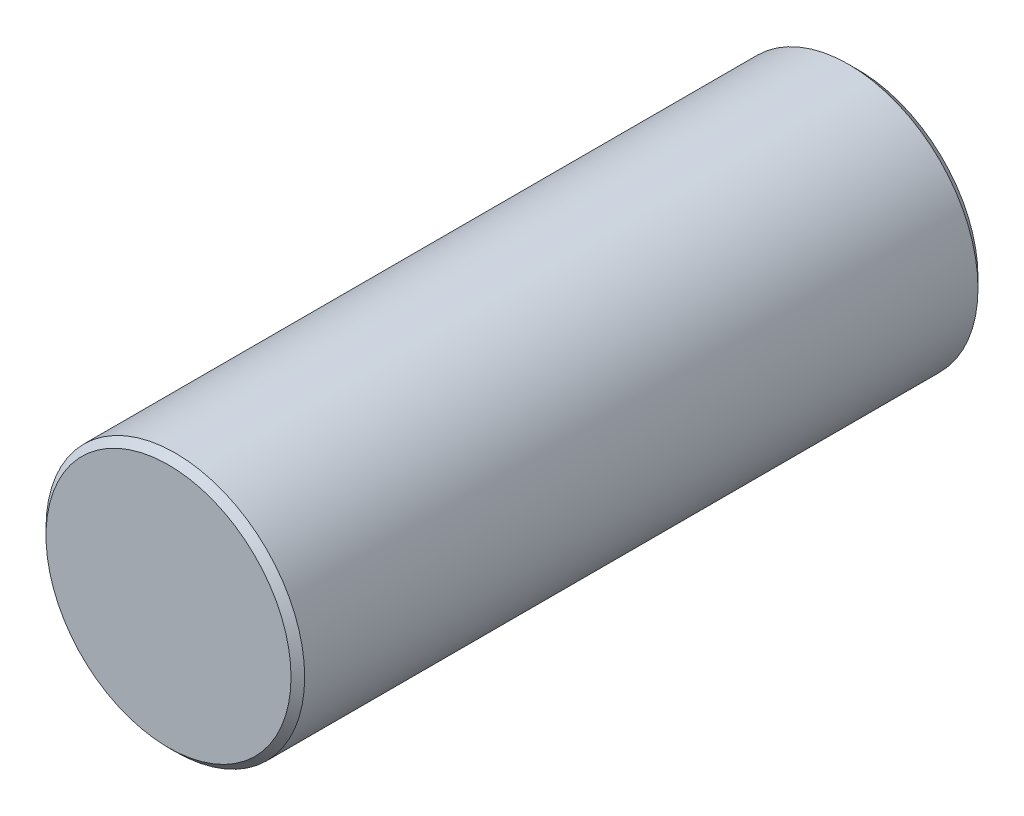
SolidWorks part; units mm, degrees
ref_plane "Front Plane" through (0, 0, 0) normal (0, 0, 1) x (1, 0, 0)
ref_plane "Top Plane" through (0, 0, 0) normal (0, 1, 0) x (1, 0, 0)
ref_plane "Right Plane" through (0, 0, 0) normal (1, 0, 0) x (0, 0, -1)
sketch "Sketch1" plane through (0, 0, 0) normal (1, 0, 0) x (0, 0, -1)
  line L0 (-12.7, 0) -> (-12.7, 4.5111)
  line L1 (-12.7, 4.5111) -> (-12.4486, 4.7625)
  line L2 (-12.4486, 4.7625) -> (12.3444, 4.7625)
  line L3 (12.3444, 4.7625) -> (12.7, 4.4069)
  line L4 (12.7, 4.4069) -> (12.7, 0)
  line L5 (12.7, 0) -> (-12.7, 0)
  line L6 (12.7, 0) -> (-12.7, 0) construction
revolve "Revolve1" add sketch "Sketch1" angle 360 about L6 reverse direction yes
ref_plane "dia1 XY" through (0, 0, 0) normal (0, 0, 1) x (1, 0, 0)
ref_plane "dia1 XZ" through (0, 0, 0) normal (0, -1, 0) x (-1, 0, 0)
ref_plane "dia1 YZ" through (-4.7625, 0, 0) normal (1, 0, 0) x (0, 0, -1)
ref_axis "dia1 X" through (-80.9, 0, 0) along (1, 0, 0)
ref_axis "dia1 Y" through (-4.7625, -50, 0) along (0, 1, 0)
ref_axis "dia1 Z" through (-4.7625, 0, 80.9) along (0, 0, -1)
sketch3d "dia1"
  point P0 (-4.7625, 0, 0)
ref_plane "dia2 XY" through (0, 0, 0) normal (0, 0, 1) x (1, 0, 0)
ref_plane "dia2 XZ" through (0, 0, 0) normal (0, -1, 0) x (-1, 0, 0)
ref_plane "dia2 YZ" through (4.7625, 0, 0) normal (1, 0, 0) x (0, 0, -1)
ref_axis "dia2 X" through (-80.9, 0, 0) along (1, 0, 0)
ref_axis "dia2 Y" through (4.7625, -50, 0) along (0, 1, 0)
ref_axis "dia2 Z" through (4.7625, 0, 80.9) along (0, 0, -1)
sketch3d "dia2"
  point P0 (4.7625, 0, 0)
ref_plane "pin XY" through (0, 0, 0) normal (0, 0, 1) x (1, 0, 0)
ref_plane "pin XZ" through (0, 0, 0) normal (0, -1, 0) x (-1, 0, 0)
ref_plane "pin YZ" through (0, 0, 0) normal (1, 0, 0) x (0, 0, -1)
ref_axis "pin X" through (-80.9, 0, 0) along (1, 0, 0)
ref_axis "pin Y" through (0, -50, 0) along (0, 1, 0)
ref_axis "pin Z" through (0, 0, 80.9) along (0, 0, -1)
sketch3d "pin"
  point P0 (0, 0, 0)
ref_plane "pin1 XY" through (0, 0, 0) normal (1, 0, 0) x (0, 0, -1)
ref_plane "pin1 XZ" through (0, 0, 0) normal (0, -1, 0) x (-1, 0, 0)
ref_plane "pin1 YZ" through (0, 0, 12.7) normal (0, 0, -1) x (-1, 0, 0)
ref_axis "pin1 X" through (0, 0, 80.9) along (0, 0, -1)
ref_axis "pin1 Y" through (0, -50, 12.7) along (0, 1, 0)
ref_axis "pin1 Z" through (80.9, 0, 12.7) along (-1, 0, 0)
sketch3d "pin1"
  point P0 (0, 0, 12.7)
ref_plane "pin2 XY" through (0, 0, 0) normal (1, 0, 0) x (0, 0, -1)
ref_plane "pin2 XZ" through (0, 0, 0) normal (0, -1, 0) x (-1, 0, 0)
ref_plane "pin2 YZ" through (0, 0, -12.7) normal (0, 0, -1) x (-1, 0, 0)
ref_axis "pin2 X" through (0, 0, 80.9) along (0, 0, -1)
ref_axis "pin2 Y" through (0, -50, -12.7) along (0, 1, 0)
ref_axis "pin2 Z" through (80.9, 0, -12.7) along (-1, 0, 0)
sketch3d "pin2"
  point P0 (0, 0, -12.7)
